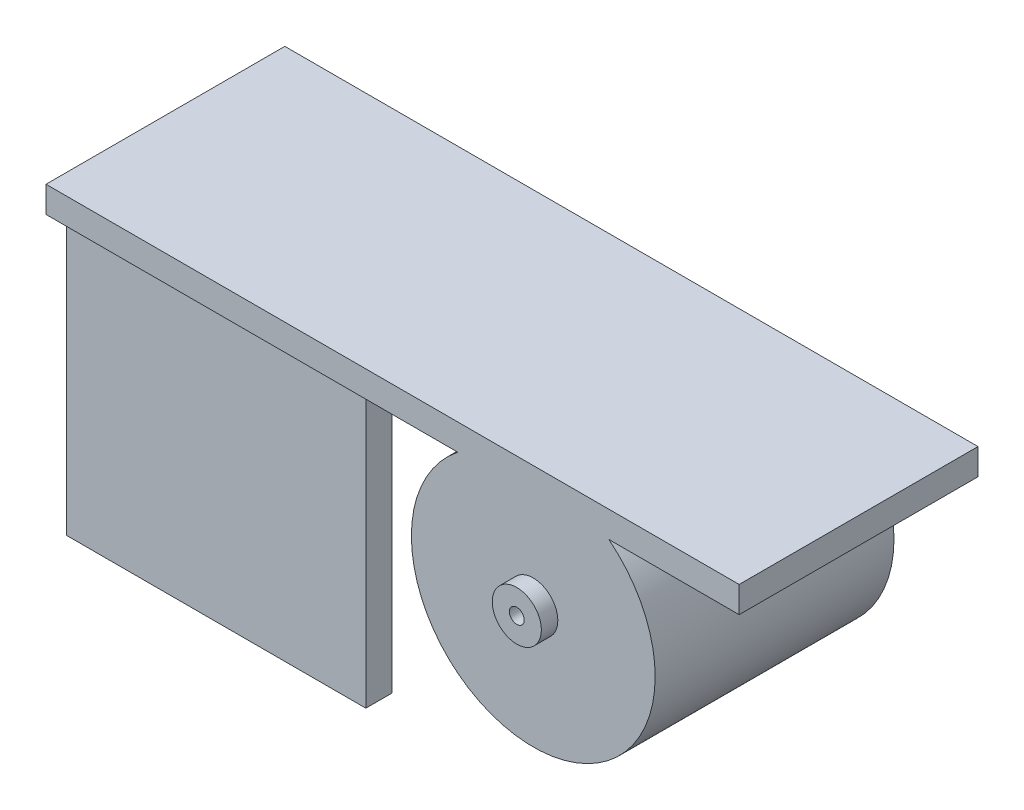
SolidWorks part; units mm, degrees
ref_plane "Front Plane" through (0, 0, 0) normal (0, 0, 1) x (1, 0, 0)
ref_plane "Top Plane" through (0, 0, 0) normal (0, 1, 0) x (1, 0, 0)
ref_plane "Right Plane" through (0, 0, 0) normal (1, 0, 0) x (0, 0, -1)
sketch "Sketch1" plane through (0, 0, 0) normal (0, 0, 1) x (1, 0, 0)
  circle A2 centre (0, 0) radius 11.8
  circle A3 centre (0, 0) radius 14.8
  dimension "D1" = 23.6
  dimension "D2" = 3
extrude "Boss-Extrude2" add sketch "Sketch1" along normal blind 23.33
sketch "Sketch2" plane through (0, 0, 23.33) normal (0, 0, 1) x (1, 0, 0)
  circle A0 centre (0, 0) radius 9.25
  circle A2 centre (0, 0) radius 14.8
  circle A3 centre (0, 0) radius 14.8
  dimension "D1" = 18.5
  dimension "D2" = 0
extrude "Boss-Extrude3" add sketch "Sketch2" along normal blind 3.34
sketch "Sketch3" plane through (0, 0, 26.67) normal (0, 0, 1) x (1, 0, 0)
  circle A0 centre (0, 0) radius 2.98
  circle A2 centre (0, 0) radius 14.8
  circle A3 centre (0, 0) radius 14.8
  dimension "D2" = 5.96
  dimension "D1" = 0
extrude "Boss-Extrude4" add sketch "Sketch3" along normal blind 2.33
sketch "Sketch4" plane through (0, 0, 29) normal (0, 0, 1) x (1, 0, 0)
  circle A0 centre (0, 0) radius 0.9
  circle A1 centre (0, 0) radius 2.98
extrude "Boss-Extrude5" add sketch "Sketch4" along normal blind 2 separate body
sketch "Sketch8" plane through (0, 0, 0) normal (0, 0, 1) x (1, 0, 0)
  line L0 (-59.166, 14.8) -> (25, 14.8)
  line L1 (-59.166, 14.8) -> (-59.166, 11.62)
  line L3 (25, 11.62) -> (25, 14.8)
  line L4 (-59.166, 11.62) -> (-9.166, 11.62)
  line L5 (9.166, 11.62) -> (25, 11.62)
  circle A3 centre (0, 0) radius 14.8 construction
  circle A4 centre (0, 0) radius 14.8
  point P3 (0, 14.8)
  point P4 (0, 14.8)
  dimension "D1" = 3.18
extrude "Boss-Extrude8" add sketch "Sketch8" along normal up to surface (29 mm away) contours A4 L0 L1 L4 | A4 L5 L3 L0 region at (-32.6675, 13.2461, 0) region at (15.5059, 13.312, 0) up to face at (14.8, 0, 29)
sketch "Sketch10" plane through (0, 11.62, 0) normal (0, -1, 0) x (1, 0, 0)
  line L0 (-59.166, 29) -> (-59.166, 0) construction
  line L1 (-59.166, 26.5) -> (-22.8307, 26.5)
  line L2 (-59.166, 26.5) -> (-59.166, 23.32)
  line L3 (-59.166, 23.32) -> (-22.8307, 23.32)
  line L4 (-22.8307, 26.5) -> (-22.8307, 23.32)
  line L5 (-59.166, 29) -> (-9.166, 29) construction
  dimension "D1" = 3.18
  dimension "D2" = 2.5
extrude "Boss-Extrude10" add sketch "Sketch10" along normal blind 35
